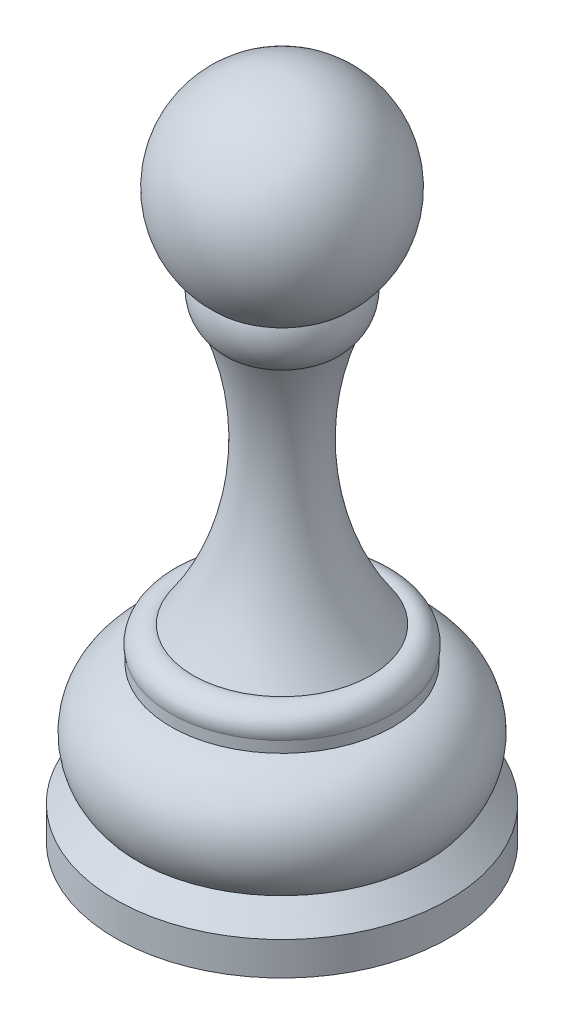
SolidWorks part; units mm, degrees
ref_plane "Front Plane" through (0, 0, 0) normal (0, 0, 1) x (1, 0, 0)
ref_plane "Top Plane" through (0, 0, 0) normal (0, 1, 0) x (1, 0, 0)
ref_plane "Right Plane" through (0, 0, 0) normal (1, 0, 0) x (0, 0, -1)
sketch "Sketch7" plane through (0, 0, 0) normal (0, 0, 1) x (1, 0, 0)
  line L0 (0, 29.4513) -> (0, -30.5487) construction
  line L1 (0, -30.5487) -> (15, -30.5487)
  line L2 (15, -30.5487) -> (15, -27.5487)
  line L3 (15, -27.5487) -> (13, -25.5487)
  line L4 (15, -30.5487) -> (10, -30.5487) construction
  line L5 (10, -30.5487) -> (10, -18.2996) construction
  line L6 (10, -16.5787) -> (10, -15.5787)
  line L7 (10, -30.5487) -> (5, -30.5487) construction
  line L8 (8, -13.5787) -> (8, 9.7431) construction
  line L9 (10.8606, -15.1362) -> (6.0246, -15.1362) construction
  line L10 (0, 9.7431) -> (0, 13.7431) construction
  line L11 (0, 9.7431) -> (5, 9.7431) construction
  line L12 (0, 13.7431) -> (6, 13.7431) construction
  line L13 (0, 29.4513) -> (0, 20.4513) construction
  line L14 (0, 29.4513) -> (0, -30.5487)
  arc A0 (13, -25.5487) -> (10, -16.5787) centre (8.6669, -22.0113) ccw
  arc A2 (10, -15.5787) -> (8, -13.5787) centre (8.4426, -15.1362) ccw
  arc A3 (5, 9.7431) -> (8, -13.5787) centre (28.3826, 0.897) ccw
  arc A4 (5, 9.7431) -> (6, 13.7431) centre (2.1745, 12.5744) ccw
  arc A5 (6, 13.7431) -> (0, 29.4513) centre (0, 20.4513) ccw
  dimension "D11" = 5
  dimension "D12" = 50
  dimension "D13" = 0.4426
  dimension "D17" = 4
  dimension "D1" = 60
  dimension "D2" = 15
  dimension "D3" = 3
  dimension "D4" = 2
  dimension "D5" = 135
  dimension "D6" = 5
  dimension "D7" = 8.97
  dimension "D8" = 1
  dimension "D9" = 5
  dimension "D14" = 2
  dimension "D15" = 6
  dimension "D16" = 4
  dimension "D18" = 9
revolve "Revolve1" add sketch "Sketch7" angle 360 about L0 region at (0.6185, -0.5487, 0)
